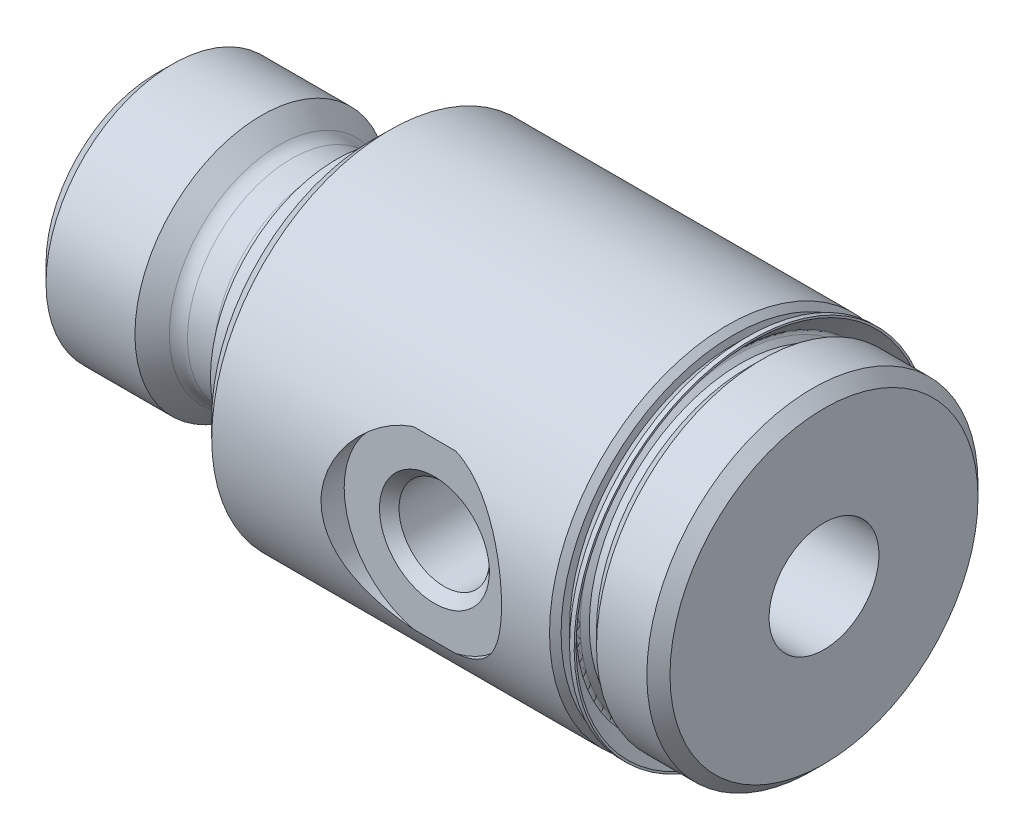
SolidWorks part; units mm, degrees
material "6061-T6 (SS)"
ref_plane "Front Plane" through (0, 0, 0) normal (0, 0, 1) x (1, 0, 0)
ref_plane "Top Plane" through (0, 0, 0) normal (0, 1, 0) x (1, 0, 0)
ref_plane "Right Plane" through (0, 0, 0) normal (1, 0, 0) x (0, 0, -1)
sketch "Sketch1" plane through (0, 0, 0) normal (0, 0, 1) x (1, 0, 0)
  line L0 (0, 0) -> (0, 4.8006)
  line L1 (0, 4.8006) -> (0.7557, 5.5563)
  line L2 (0.7557, 5.5563) -> (4.6603, 5.5563)
  line L3 (4.6603, 5.5563) -> (5.4181, 4.8042)
  line L4 (5.9817, 4.572) -> (7.1501, 4.572)
  line L5 (7.9502, 5.3721) -> (7.9502, 5.5309)
  line L6 (7.9502, 5.5309) -> (9.525, 5.5309)
  line L7 (9.525, 5.5309) -> (9.525, 0)
  line L8 (9.525, 0) -> (0, 0)
  line L9 (9.525, 0) -> (0, 0) construction
  arc A0 (5.4181, 4.8042) -> (5.9817, 4.572) centre (5.9817, 5.3721) ccw
  arc A1 (7.1501, 4.572) -> (7.9502, 5.3721) centre (7.1501, 5.3721) ccw
revolve "Revolve1" add sketch "Sketch1" angle 360 about L9 reverse direction yes
cosmetic thread "Cosmetic Thread1" parameters "D1"=5.4159, "D2"=9.6012
sketch "Sketch2" plane through (0, 0, 0) normal (0, 0, 1) x (1, 0, 0)
  line L0 (9.525, 0) -> (9.525, 7.0485)
  line L1 (9.525, 7.0485) -> (10.287, 7.8105)
  line L2 (10.287, 7.8105) -> (25.1206, 7.8105)
  line L3 (25.1206, 7.8105) -> (25.3746, 7.5565)
  line L4 (25.3746, 7.5565) -> (25.3746, 6.6357)
  line L5 (25.3746, 6.6357) -> (26.0096, 6.6357)
  line L6 (26.0096, 6.6357) -> (26.6446, 7.2707)
  line L7 (26.6446, 7.2707) -> (28.8544, 7.2707)
  line L8 (28.8544, 7.2707) -> (29.3624, 6.7627)
  line L9 (29.3624, 6.7627) -> (29.3624, 0)
  line L10 (29.3624, 0) -> (9.525, 0)
  line L11 (29.3624, 0) -> (9.525, 0) construction
revolve "Revolve2" add sketch "Sketch2" angle 360 about L11 reverse direction yes
sketch "Sketch3" plane through (0, 0, 0) normal (0, 0, 1) x (1, 0, 0)
  line L0 (0, 0) -> (0, 2.921)
  line L1 (0, 2.921) -> (0.508, 2.413)
  line L2 (0.508, 2.413) -> (29.3624, 2.413)
  line L3 (29.3624, 2.413) -> (29.3624, 0)
  line L4 (29.3624, 0) -> (0, 0)
  line L5 (29.3624, 0) -> (0, 0) construction
revolve "Cut-Revolve1" cut sketch "Sketch3" angle 360 about L5 reverse direction yes
sketch "Sketch4" plane through (0, 0, 0) normal (0, 1, 0) x (1, 0, 0)
  line L0 (19.05, 1.016) -> (21.0337, 1.016)
  line L1 (21.0337, 1.016) -> (21.0337, -6.3652)
  line L2 (21.0337, -6.3652) -> (21.463, -6.7945)
  line L3 (21.463, -6.7945) -> (23.0124, -6.7945)
  line L4 (23.0124, -6.7945) -> (23.0124, -7.8105)
  line L5 (23.0124, -7.8105) -> (19.05, -7.8105)
  line L6 (19.05, -7.8105) -> (19.05, 1.016)
  line L7 (19.05, -7.8105) -> (19.05, 1.016) construction
revolve "Cut-Revolve2" cut sketch "Sketch4" angle 360 about L7 reverse direction yes
cosmetic thread "Cosmetic Thread2" parameters "D1"=2.4257, "D2"=4.826
ref_plane "Plane1" through (0, 0, 0) normal (1, 0, 0) x (0, 0, -1)
ref_plane "Plane2" through (0, 0, 0) normal (1, 0, 0) x (0, 0, -1)
ref_plane "Plane3" through (0, 0, 0) normal (0, -0.7071, 0.7071) x (1, 0, 0)
ref_plane "Plane4" through (0, 0, 0) normal (1, 0, 0) x (0, 0, -1)
ref_plane "Plane5" through (25.4, 0, 0) normal (1, 0, 0) x (0, 0, -1)
ref_plane "Plane6" through (9.525, 0, 0) normal (1, 0, 0) x (0, 0, -1)
ref_plane "Plane7" through (25.4, 0, 0) normal (1, 0, 0) x (0, 0, -1)
sketch "Sketch5" plane through (0, 0, 0) normal (0, 0, 1) x (1, 0, 0)
  line L0 (25.3746, 7.1861) -> (25.3746, 6.3818)
  line L1 (25.3746, 6.3818) -> (26.0096, 6.3818)
  line L2 (26.0096, 6.3818) -> (26.0096, 6.6357)
  line L3 (26.0096, 6.6357) -> (25.6921, 6.6357)
  line L4 (25.6921, 6.6357) -> (25.4916, 6.8362)
  line L5 (25.4916, 7.0158) -> (26.2022, 7.7263)
  line L6 (26.2022, 7.7263) -> (26.2022, 7.8105)
  line L7 (26.2022, 7.8105) -> (25.999, 7.8105)
  line L8 (25.999, 7.8105) -> (25.3746, 7.1861)
  line L9 (26.0096, 0) -> (25.3746, 0) construction
  arc A0 (25.4916, 6.8362) -> (25.4916, 7.0158) centre (25.5814, 6.926) cw
revolve "Revolve3" add sketch "Sketch5" angle 360 about L9 reverse direction yes
ref_plane "Plane8" through (26.0096, 0, 0) normal (1, 0, 0) x (0, 0, -1)
ref_plane "Plane9" through (9.525, 0, 0) normal (1, 0, 0) x (0, 0, -1)
ref_plane "Plane10" through (7.9502, 0, 0) normal (1, 0, 0) x (0, 0, -1)
ref_plane "Plane11" through (0, 0, 0) normal (0, 1, 0) x (1, 0, 0)
ref_plane "Plane12" through (0, 0, 0) normal (0, 1, 0) x (1, 0, 0)
ref_plane "Plane13" through (9.525, 0, 0) normal (1, 0, 0) x (0, 0, -1)
ref_plane "Plane14" through (0, 0, 0) normal (0, 0, 1) x (1, 0, 0)
ref_plane "Plane15" through (0, 0, 0) normal (0, 1, 0) x (1, 0, 0)
ref_plane "Plane16" through (0, 0, 0) normal (0, 1, 0) x (1, 0, 0)
ref_plane "Plane17" through (0, 0, 0) normal (0, 1, 0) x (1, 0, 0)
ref_plane "Plane18" through (0, 0, 0) normal (1, 0, 0) x (0, 0, -1)
ref_plane "dp1 XY" through (0, 0, 0) normal (0, 0, 1) x (1, 0, 0)
ref_plane "dp1 XZ" through (0, 5.5309, 0) normal (0, -1, 0) x (-1, 0, 0)
ref_plane "dp1 YZ" through (9.525, 0, 0) normal (1, 0, 0) x (0, 0, -1)
ref_axis "dp1 X" through (-80.9, 5.5309, 0) along (1, 0, 0)
ref_axis "dp1 Y" through (9.525, -50, 0) along (0, 1, 0)
ref_axis "dp1 Z" through (9.525, 5.5309, 80.9) along (0, 0, -1)
sketch3d "dp1"
  point P0 (9.525, 5.5309, 0)
ref_plane "dp2 XY" through (0, 0, 0) normal (0, 0, 1) x (1, 0, 0)
ref_plane "dp2 XZ" through (0, -5.5309, 0) normal (0, -1, 0) x (-1, 0, 0)
ref_plane "dp2 YZ" through (9.525, 0, 0) normal (1, 0, 0) x (0, 0, -1)
ref_axis "dp2 X" through (-80.9, -5.5309, 0) along (1, 0, 0)
ref_axis "dp2 Y" through (9.525, -50, 0) along (0, 1, 0)
ref_axis "dp2 Z" through (9.525, -5.5309, 80.9) along (0, 0, -1)
sketch3d "dp2"
  point P0 (9.525, -5.5309, 0)
ref_plane "port XY" through (0, 0, 0) normal (0, 0, 1) x (1, 0, 0)
ref_plane "port XZ" through (0, 0, 0) normal (0, -1, 0) x (-1, 0, 0)
ref_plane "port YZ" through (19.05, 0, 0) normal (1, 0, 0) x (0, 0, -1)
ref_axis "port X" through (-80.9, 0, 0) along (1, 0, 0)
ref_axis "port Y" through (19.05, -50, 0) along (0, 1, 0)
ref_axis "port Z" through (19.05, 0, 80.9) along (0, 0, -1)
sketch3d "port"
  point P0 (19.05, 0, 0)
ref_plane "rod_guide XY" through (0, 0, 0) normal (1, 0, 0) x (0, 0, -1)
ref_plane "rod_guide XZ" through (0, 0, 0) normal (0, -1, 0) x (-1, 0, 0)
ref_plane "rod_guide YZ" through (0, 0, 0) normal (0, 0, -1) x (-1, 0, 0)
ref_axis "rod_guide X" through (0, 0, 80.9) along (0, 0, -1)
ref_axis "rod_guide Y" through (0, -50, 0) along (0, 1, 0)
ref_axis "rod_guide Z" through (80.9, 0, 0) along (-1, 0, 0)
sketch3d "rod_guide"
  point P0 (0, 0, 0)
ref_plane "s1 XY" through (0, 0, 0) normal (0, 0, 1) x (1, 0, 0)
ref_plane "s1 XZ" through (0, 0, 0) normal (0, -1, 0) x (-1, 0, 0)
ref_plane "s1 YZ" through (7.9502, 0, 0) normal (1, 0, 0) x (0, 0, -1)
ref_axis "s1 X" through (-80.9, 0, 0) along (1, 0, 0)
ref_axis "s1 Y" through (7.9502, -50, 0) along (0, 1, 0)
ref_axis "s1 Z" through (7.9502, 0, 80.9) along (0, 0, -1)
sketch3d "s1"
  point P0 (7.9502, 0, 0)
ref_plane "s2 XY" through (0, 0, 0) normal (0, 0, 1) x (1, 0, 0)
ref_plane "s2 XZ" through (0, 0, 0) normal (0, -1, 0) x (-1, 0, 0)
ref_plane "s2 YZ" through (9.525, 0, 0) normal (1, 0, 0) x (0, 0, -1)
ref_axis "s2 X" through (-80.9, 0, 0) along (1, 0, 0)
ref_axis "s2 Y" through (9.525, -50, 0) along (0, 1, 0)
ref_axis "s2 Z" through (9.525, 0, 80.9) along (0, 0, -1)
sketch3d "s2"
  point P0 (9.525, 0, 0)
ref_plane "t1 XY" through (9.525, 0, 0) normal (1, 0, 0) x (0, 0, -1)
ref_plane "t1 XZ" through (0, 0, 0) normal (0, -1, 0) x (-1, 0, 0)
ref_plane "t1 YZ" through (0, 0, 0) normal (0, 0, -1) x (-1, 0, 0)
ref_axis "t1 X" through (9.525, 0, 80.9) along (0, 0, -1)
ref_axis "t1 Y" through (9.525, -50, 0) along (0, 1, 0)
ref_axis "t1 Z" through (80.9, 0, 0) along (-1, 0, 0)
sketch3d "t1"
  point P0 (9.525, 0, 0)
ref_plane "t111 XY" through (9.525, 0, 0) normal (1, 0, 0) x (0, 0, -1)
ref_plane "t111 XZ" through (0, 0, 0) normal (0, -1, 0) x (-1, 0, 0)
ref_plane "t111 YZ" through (0, 0, 0) normal (0, 0, -1) x (-1, 0, 0)
ref_axis "t111 X" through (9.525, 0, 80.9) along (0, 0, -1)
ref_axis "t111 Y" through (9.525, -50, 0) along (0, 1, 0)
ref_axis "t111 Z" through (80.9, 0, 0) along (-1, 0, 0)
sketch3d "t111"
  point P0 (9.525, 0, 0)
ref_plane "to_foot_bracket XY" through (9.525, 0, 0) normal (1, 0, 0) x (0, 0, -1)
ref_plane "to_foot_bracket XZ" through (0, 0, 0) normal (0, -1, 0) x (-1, 0, 0)
ref_plane "to_foot_bracket YZ" through (0, 0, 0) normal (0, 0, -1) x (-1, 0, 0)
ref_axis "to_foot_bracket X" through (9.525, 0, 80.9) along (0, 0, -1)
ref_axis "to_foot_bracket Y" through (9.525, -50, 0) along (0, 1, 0)
ref_axis "to_foot_bracket Z" through (80.9, 0, 0) along (-1, 0, 0)
sketch3d "to_foot_bracket"
  point P0 (9.525, 0, 0)
ref_plane "to_nut XY" through (7.9502, 0, 0) normal (1, 0, 0) x (0, 0, -1)
ref_plane "to_nut XZ" through (0, 0, 0) normal (0, -1, 0) x (-1, 0, 0)
ref_plane "to_nut YZ" through (0, 0, 0) normal (0, 0, -1) x (-1, 0, 0)
ref_axis "to_nut X" through (7.9502, 0, 80.9) along (0, 0, -1)
ref_axis "to_nut Y" through (7.9502, -50, 0) along (0, 1, 0)
ref_axis "to_nut Z" through (80.9, 0, 0) along (-1, 0, 0)
sketch3d "to_nut"
  point P0 (7.9502, 0, 0)
ref_plane "to_rod XY" through (0, 0, 0) normal (1, 0, 0) x (0, 0, -1)
ref_plane "to_rod XZ" through (0, 0, 0) normal (0, -1, 0) x (-1, 0, 0)
ref_plane "to_rod YZ" through (0, 0, 0) normal (0, 0, -1) x (-1, 0, 0)
ref_axis "to_rod X" through (0, 0, 80.9) along (0, 0, -1)
ref_axis "to_rod Y" through (0, -50, 0) along (0, 1, 0)
ref_axis "to_rod Z" through (80.9, 0, 0) along (-1, 0, 0)
sketch3d "to_rod"
  point P0 (0, 0, 0)
ref_plane "to_screw XY" through (0, 0, 0) normal (0, 1, 0) x (1, 0, 0)
ref_plane "to_screw XZ" through (0, 0, 0) normal (0, 0, 1) x (1, 0, 0)
ref_plane "to_screw YZ" through (19.05, 0, 0) normal (1, 0, 0) x (0, 0, -1)
ref_axis "to_screw X" through (-80.9, 0, 0) along (1, 0, 0)
ref_axis "to_screw Y" through (19.05, 0, 50) along (0, 0, -1)
ref_axis "to_screw Z" through (19.05, 50, 0) along (0, -1, 0)
sketch3d "to_screw"
  point P0 (19.05, 0, 0)
ref_plane "to_trunnion_brackets XY" through (0, 0, 0) normal (0, 1, 0) x (1, 0, 0)
ref_plane "to_trunnion_brackets XZ" through (0, 0, 0) normal (0, 0, 1) x (1, 0, 0)
ref_plane "to_trunnion_brackets YZ" through (0, 0, 0) normal (1, 0, 0) x (0, 0, -1)
ref_axis "to_trunnion_brackets X" through (-80.9, 0, 0) along (1, 0, 0)
ref_axis "to_trunnion_brackets Y" through (0, 0, 50) along (0, 0, -1)
ref_axis "to_trunnion_brackets Z" through (0, 50, 0) along (0, -1, 0)
sketch3d "to_trunnion_brackets"
  point P0 (0, 0, 0)
ref_plane "to_trunnion_brackets1 XY" through (0, 0, 0) normal (0, 1, 0) x (1, 0, 0)
ref_plane "to_trunnion_brackets1 XZ" through (0, 0, 0) normal (0, 0, 1) x (1, 0, 0)
ref_plane "to_trunnion_brackets1 YZ" through (0, 0, 0) normal (1, 0, 0) x (0, 0, -1)
ref_axis "to_trunnion_brackets1 X" through (-80.9, 0, 0) along (1, 0, 0)
ref_axis "to_trunnion_brackets1 Y" through (0, 0, 50) along (0, 0, -1)
ref_axis "to_trunnion_brackets1 Z" through (0, 50, 0) along (0, -1, 0)
sketch3d "to_trunnion_brackets1"
  point P0 (0, 0, 0)
ref_plane "to_trunnion_brackets2 XY" through (0, 0, 0) normal (0, 1, 0) x (1, 0, 0)
ref_plane "to_trunnion_brackets2 XZ" through (0, 0, 0) normal (0, 0, 1) x (1, 0, 0)
ref_plane "to_trunnion_brackets2 YZ" through (0, 0, 0) normal (1, 0, 0) x (0, 0, -1)
ref_axis "to_trunnion_brackets2 X" through (-80.9, 0, 0) along (1, 0, 0)
ref_axis "to_trunnion_brackets2 Y" through (0, 0, 50) along (0, 0, -1)
ref_axis "to_trunnion_brackets2 Z" through (0, 50, 0) along (0, -1, 0)
sketch3d "to_trunnion_brackets2"
  point P0 (0, 0, 0)
ref_plane "to_tube XY" through (26.0096, 0, 0) normal (1, 0, 0) x (0, 0, -1)
ref_plane "to_tube XZ" through (0, 0, 0) normal (0, -1, 0) x (-1, 0, 0)
ref_plane "to_tube YZ" through (0, 0, 0) normal (0, 0, -1) x (-1, 0, 0)
ref_axis "to_tube X" through (26.0096, 0, 80.9) along (0, 0, -1)
ref_axis "to_tube Y" through (26.0096, -50, 0) along (0, 1, 0)
ref_axis "to_tube Z" through (80.9, 0, 0) along (-1, 0, 0)
sketch3d "to_tube"
  point P0 (26.0096, 0, 0)
